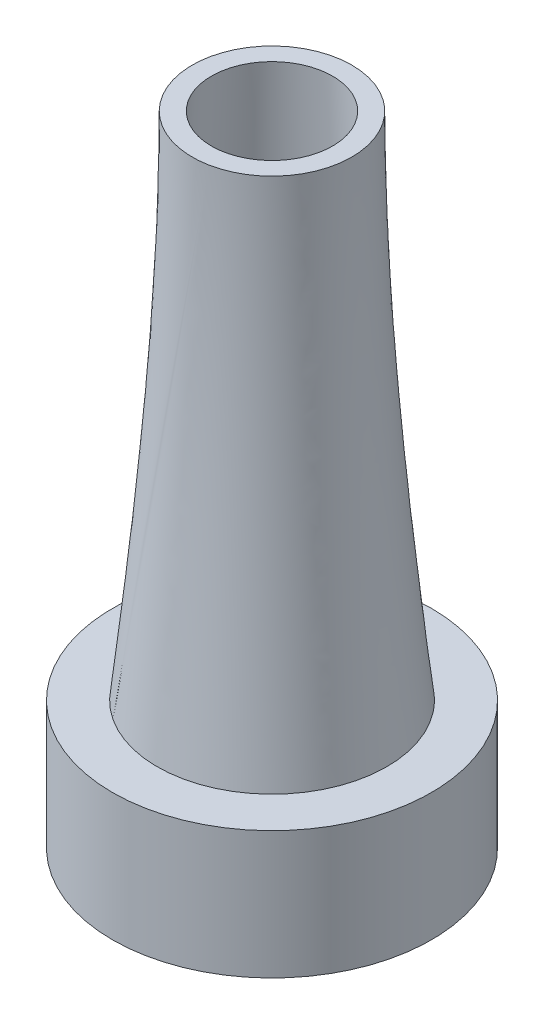
SolidWorks part; units mm, degrees
material "Caucho natural"
ref_plane "Alzado" through (0, 0, 0) normal (0, 0, 1) x (1, 0, 0)
ref_plane "Planta" through (0, 0, 0) normal (0, 1, 0) x (1, 0, 0)
ref_plane "Vista lateral" through (0, 0, 0) normal (1, 0, 0) x (0, 0, -1)
sketch "Croquis1" plane through (0, 0, 0) normal (0, 1, 0) x (1, 0, 0)
  circle A0 centre (0, 0) radius 25
  dimension "D1" = 50
extrude "Saliente-Extruir1" add sketch "Croquis1" along normal blind 20
sketch "Croquis2" plane through (0, 20, 0) normal (0, 1, 0) x (1, 0, 0)
  circle A0 centre (0, 0) radius 18
  dimension "D1" = 36
ref_plane "Plano2" through (0, 100, 0) normal (0, 1, 0) x (1, 0, 0)
sketch "Croquis4" plane through (0, 100, 0) normal (0, 1, 0) x (1, 0, 0)
  circle A1 centre (0, 0) radius 12.5
  dimension "D1" = 25
loft "Recubrir1" add section "Croquis2" section "Croquis4" connector at (-9.8446, 20, 15.0693) connector at (2.3885, 100, 12.2697)
sketch "Croquis5" plane through (0, 100, 0) normal (0, 1, 0) x (1, 0, 0)
  circle A0 centre (0, 0) radius 9.5
  circle A1 centre (0, 0) radius 12.5 construction
  dimension "D1" = 3
extrude "Cortar-Extruir1" cut sketch "Croquis5" against normal blind 80 draft 3 draft outward yes
